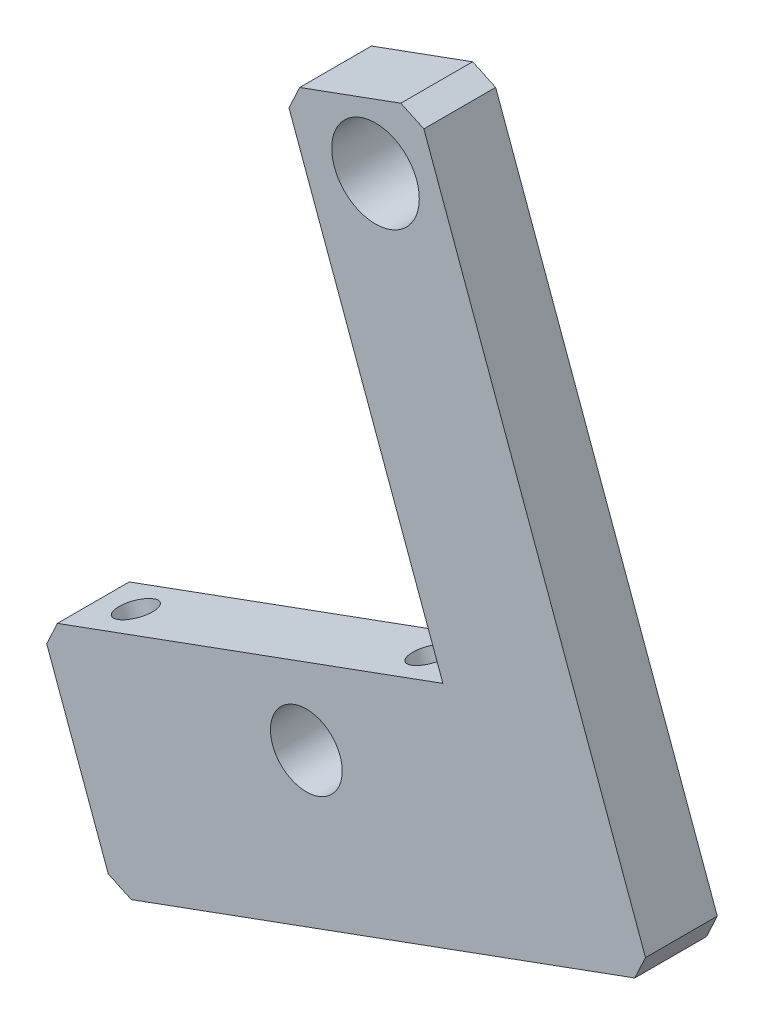
SolidWorks part; units mm, degrees
ref_plane "前基準面" through (0, 0, 0) normal (0, 0, 1) x (1, 0, 0)
ref_plane "上基準面" through (0, 0, 0) normal (0, 1, 0) x (1, 0, 0)
ref_plane "右基準面" through (0, 0, 0) normal (1, 0, 0) x (0, 0, -1)
sketch "草圖1" plane through (0, 0, 0) normal (0, 0, 1) x (1, 0, 0)
  line L0 (-29.9561, 9.7552) -> (-48.7426, 2.8947)
  line L2 (-48.7426, 2.8947) -> (-26.446, -58.1615)
  line L3 (-26.446, -58.1615) -> (-82.4902, -78.6278)
  line L4 (-82.4902, -78.6278) -> (-72.1995, -106.8076)
  line L5 (-72.1995, -106.8076) -> (2.6312, -79.4808)
  line L6 (2.6312, -79.4808) -> (-29.9561, 9.7552)
  circle A0 centre (-35.8357, -1.3461) radius 6.1
  dimension "D4" = 12.2
  dimension "D1" = 20
  dimension "D2" = 30
  dimension "D3" = 65
extrude "填料-伸長1" add sketch "草圖1" along normal blind 10
sketch "草圖2" plane through (15.6286, -42.7967, 0) normal (-0.343, 0.9393, 0) x (0.9393, 0.343, 0)
  circle A0 centre (-95.6715, -4.9822) radius 2.5
  circle A1 centre (-52.1263, -4.9822) radius 2.5
  dimension "D1" = 5
  dimension "D2" = 5
extrude "除料-伸長2" cut sketch "草圖2" against normal through all
chamfer "導角1" distance 2.5 angle 45 5 edges at (-29.9561, 9.7552, 5) (-48.7426, 2.8947, 5) (2.6312, -79.4808, 5) (-72.1995, -106.8076, 5) (-82.4902, -78.6278, 5)
sketch "草圖3" plane through (0, 0, 0) normal (0, 0, -1) x (-1, 0, 0)
  line L0 (152.0261, -114.667) -> (6.0939, -61.3752) construction
  circle A0 centre (45.4703, -75.7548) radius 5
  point P5 (79.06, -88.0211)
extrude "除料-伸長3" cut sketch "草圖3" against normal through all
